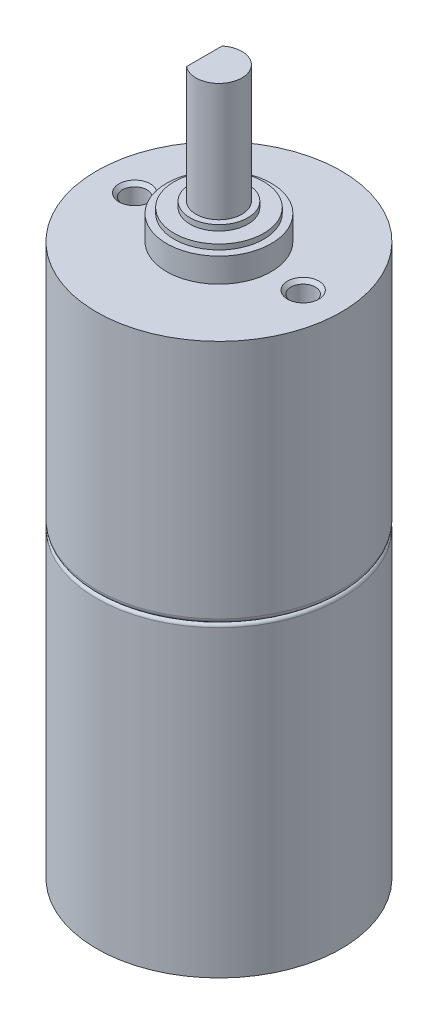
SolidWorks part; units mm, degrees
ref_plane "Front Plane" through (0, 0, 0) normal (0, 0, 1) x (1, 0, 0)
ref_plane "Top Plane" through (0, 0, 0) normal (0, 1, 0) x (1, 0, 0)
ref_plane "Right Plane" through (0, 0, 0) normal (1, 0, 0) x (0, 0, -1)
sketch "Sketch1" plane through (0, 0, 0) normal (0, 0, 1) x (1, 0, 0)
  line L0 (-6.8756, 124.9163) -> (4.1244, 124.9147) construction
  dimension "D1" = 11
sketch "Sketch2" plane through (0, 0, 0) normal (0, 0, 1) x (1, 0, 0)
  line L0 (0, 0) -> (2.713, 0)
  line L1 (2.713, 0) -> (2.713, 1.0579)
  line L2 (2.713, 1.0579) -> (7.9883, 1.0579)
  line L3 (7.9883, 1.0579) -> (7.9883, 20.8635)
  line L4 (7.9883, 21.3623) -> (7.9883, 37.0579)
  line L5 (7.9883, 37.0579) -> (3.4163, 37.0579)
  line L6 (3.4163, 37.0579) -> (3.4163, 38.6464)
  line L7 (3.4163, 38.6464) -> (2.9249, 38.6464)
  line L8 (2.9249, 38.6464) -> (2.9249, 38.9821)
  line L9 (2.9249, 38.9821) -> (1.8886, 38.9821)
  line L10 (1.8886, 38.9821) -> (1.8886, 39.3464)
  line L11 (1.8886, 39.3464) -> (1.5, 39.3464)
  line L12 (1.5, 39.3464) -> (1.5, 47.0579)
  line L13 (1.5, 47.0579) -> (0, 47.0579)
  line L15 (0, 47.0579) -> (0, 0)
  arc A0 (7.9883, 21.3623) -> (7.8103, 21.0579) centre (7.6389, 21.3623) cw
  arc A1 (7.9883, 20.8635) -> (7.8103, 21.0579) centre (7.7932, 20.8635) ccw
  point P19 (0, 0)
  point P20 (0, 0)
  point P21 (-12.4158, 30.7193)
  point P22 (0, 0)
  point P24 (0, 0)
  point P25 (-56.8848, 23.4663)
  dimension "D9" = 0.3494
  dimension "D10" = 0.1951
  dimension "D1" = 1.0579
  dimension "D2" = 20
  dimension "D3" = 1.5885
  dimension "D4" = 0.7
  dimension "D5" = 10
  dimension "D6" = 7.8103
  dimension "D7" = 1.5
  dimension "D8" = 3.4163
  dimension "D11" = 1.8886
  dimension "D12" = 2.713
  dimension "D13" = 2.9249
  dimension "D14" = 7.9883
  dimension "D15" = 0.3357
  dimension "D17" = 16
ref_axis "Axis1" through (0, 49.4107, 0) along (0, -1, 0)
revolve "Revolve1" add sketch "Sketch2" angle 360 about L15
hole_wizard "M2x0.4 Tapped Hole1" positions "Sketch3" profile "Sketch5" tap size "M2x0.4" standard "ANSI Metric"
sketch "Sketch3" plane through (0, 37.0579, 0) normal (0, 1, 0) x (1, 0, 0)
  line L0 (-0.0284, 0) -> (-13.6319, 0) construction
  point P0 (-5.5, 0)
  point P2 (5.5, 0)
  point P11 (0, 0)
  point P12 (0, 0)
  point P14 (5.5712, 0.8824)
  dimension "D1" = 11
  dimension "D2" = 5.5
cosmetic thread "Hole Thread1" parameters "D1"=10, "D2"=2
cosmetic thread "Hole Thread2" parameters "D1"=10, "D2"=2
sketch "Sketch5" plane through (-5.5, 37.0579, 0) normal (1, 0, 0) x (0, 0, 1)
  line L0 (0, 0) -> (0, 12.4807)
  line L1 (0, 12.4807) -> (0.8, 12)
  line L2 (0.8, 12) -> (0.8, 0.225)
  line L3 (0.8, 0.225) -> (1.025, 0)
  line L5 (1.025, 0) -> (0, 0)
  line L6 (-0.8, 0.225) -> (-1.025, 0) construction
  line L10 (0, 12.4807) -> (-0.8, 12) construction
  line L11 (0, -6.35) -> (0, 107.95) construction
  dimension "Tap Drill Dia." = 1.6
  dimension "Tap Drill Depth" = 12
  dimension "Near C'Sink Dia." = 2.05
  dimension "Near C'Sink Angle" = 90
  dimension "Drill Angle" = 118
sketch "Sketch6" plane through (0, 47.0579, 0) normal (0, 1, 0) x (1, 0, 0)
  line L0 (-0.9525, -1.1588) -> (-0.9525, 1.1588)
  circle A0 centre (0, 0) radius 1.5
  circle M3 centre (0, 0) radius 1.5
  dimension "D1" = 3
  dimension "D2" = 0.9525
extrude "Cut-Extrude1" cut sketch "Sketch6" against normal blind 5.0165 contours L0 M3 region at (-1.1753, 47.0579, 0)
